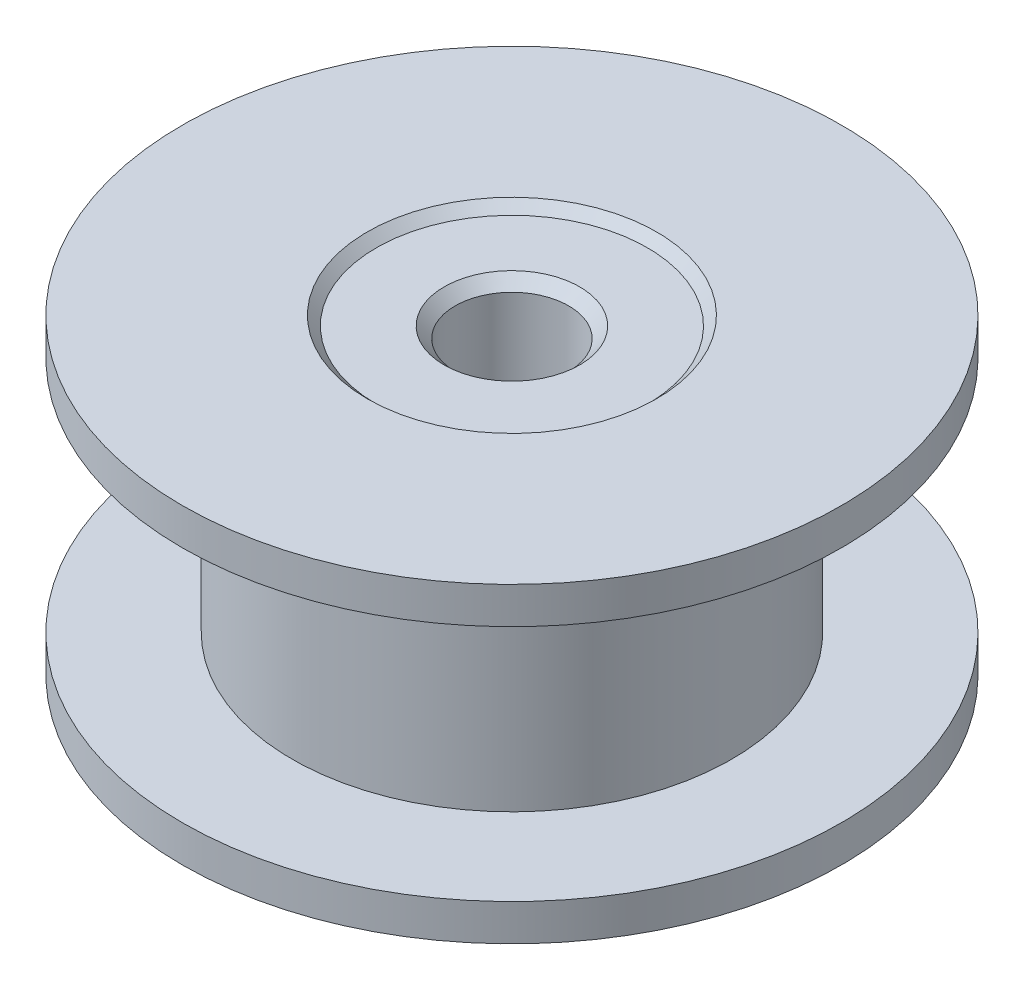
SolidWorks part; units mm, degrees
ref_plane "Front Plane" through (0, 0, 0) normal (0, 0, 1) x (1, 0, 0)
ref_plane "Top Plane" through (0, 0, 0) normal (0, 1, 0) x (1, 0, 0)
ref_plane "Right Plane" through (0, 0, 0) normal (1, 0, 0) x (0, 0, -1)
sketch "Sketch1" plane through (0, 0, 0) normal (0, 1, 0) x (1, 0, 0)
  circle A0 centre (0, 0) radius 6
  dimension "D1" = 12
extrude "Boss-Extrude1" add sketch "Sketch1" along normal mid plane 6.5
sketch "Sketch2" plane through (0, 3.25, 0) normal (0, 1, 0) x (1, 0, 0)
  circle A0 centre (0, 0) radius 9
  dimension "D1" = 18
extrude "Boss-Extrude2" add sketch "Sketch2" along normal blind 1
mirror "Mirror3" about plane through (0, 0, 0) normal (0, 1, 0) of "Boss-Extrude2"
sketch "Sketch4" plane through (0, -4.25, 0) normal (0, -1, 0) x (1, 0, 0)
  circle A0 centre (0, 0) radius 4
  dimension "D1" = 8
extrude "Cut-Extrude1" cut sketch "Sketch4" against normal through all
sketch "Sketch7" plane through (0, 0, 0) normal (0, 1, 0) x (1, 0, 0)
  circle A0 centre (0, 0) radius 4
  circle A1 centre (0, 0) radius 1.55
  dimension "D1" = 8
  dimension "D2" = 3.1
extrude "Boss-Extrude4" add sketch "Sketch7" against normal mid plane 8
chamfer "Chamfer2" distance 0.3 angle 45 4 edges at (0, 4, 1.55) (0, 4, 4) (0, -4, 4) (0, -4, 1.55)
